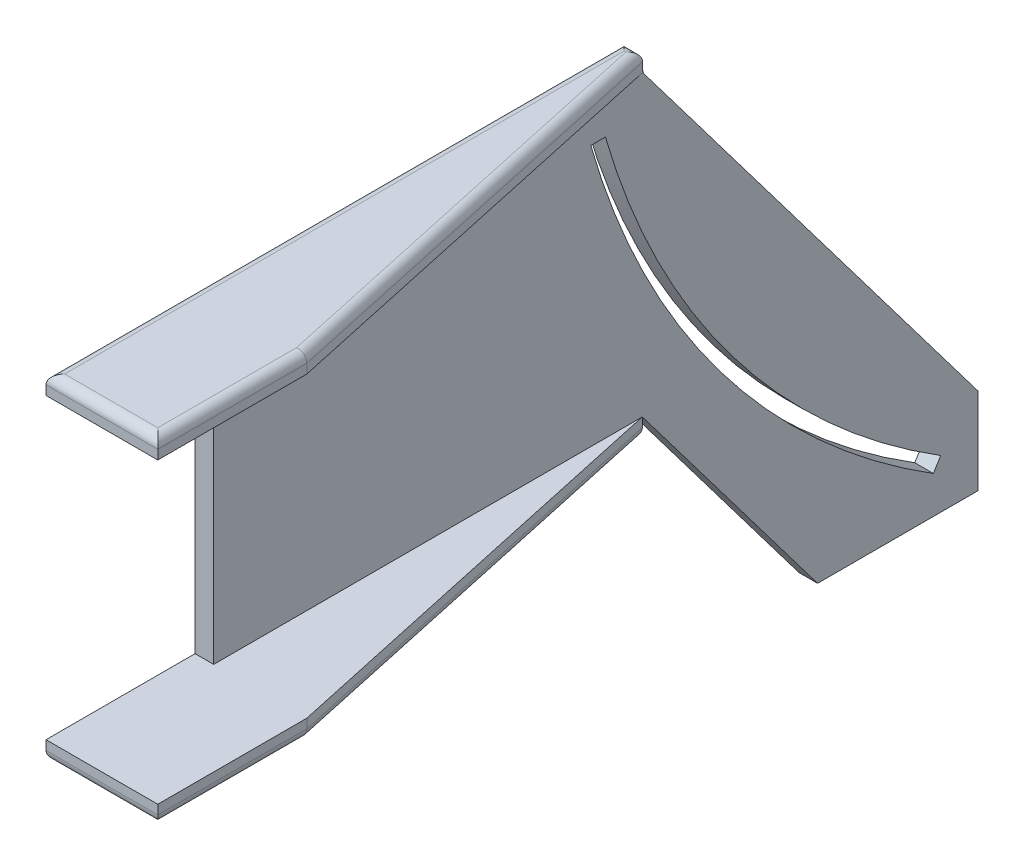
SolidWorks part; units mm, degrees
ref_plane "Front Plane" through (0, 0, 0) normal (0, 0, 1) x (1, 0, 0)
ref_plane "Top Plane" through (0, 0, 0) normal (0, 1, 0) x (1, 0, 0)
ref_plane "Right Plane" through (0, 0, 0) normal (1, 0, 0) x (0, 0, -1)
sketch "Sketch1" plane through (0, 0, 0) normal (1, 0, 0) x (0, 0, -1)
  line L0 (-129.391, -36.576) -> (-126.9146, -36.576)
  line L1 (-71.0224, -114.1738) -> (-69.7646, -112.1518)
  line L2 (-120.5646, -30.226) -> (-63.4146, -105.8018)
  line L3 (-193.675, -30.226) -> (-120.5646, -30.226)
  line L4 (-193.675, -30.226) -> (-193.675, -81.026)
  line L5 (-90.7526, -120.5238) -> (-63.4146, -120.5238)
  line L6 (-63.4146, -105.8018) -> (-63.4146, -120.5238)
  line L7 (-193.675, -81.026) -> (-120.6206, -81.026)
  line L8 (-120.6206, -81.026) -> (-90.7526, -120.5238)
  arc A0 (-126.9146, -36.576) -> (-69.7646, -112.1518) centre (0, 0) ccw
  arc A1 (-129.391, -36.576) -> (-71.0224, -114.1738) centre (0, 0) ccw
  point P14 (-128.1528, -36.576)
  dimension "D1" = 132.08
  dimension "D2" = 2.3813
  dimension "D3" = 193.675
  dimension "D4" = 6.35
  dimension "D5" = 6.35
  dimension "D6" = 6.35
  dimension "D7" = 6.35
  dimension "D8" = 6.35
  dimension "D9" = 57.15
  dimension "D10" = 30.226
  dimension "D11" = 0
  dimension "D12" = 50.8
extrude "Boss-Extrude1" add sketch "Sketch1" along normal blind 3.175
sketch "Sketch2" plane through (0, -30.226, 0) normal (0, 1, 0) x (1, 0, 0)
  line L0 (3.175, -193.675) -> (0, -193.675) construction
  line L1 (0, -120.5646) -> (3.175, -120.5646)
  line L2 (0, -120.5646) -> (0, -219.075)
  line L3 (0, -219.075) -> (19.05, -219.075)
  line L4 (19.05, -193.675) -> (19.05, -219.075)
  line L5 (3.175, -120.5646) -> (19.05, -193.675)
  point P8 (1.5875, -193.675)
  dimension "D1" = 25.4
  dimension "D2" = 19.05
  dimension "D3" = 0
extrude "Boss-Extrude2" add sketch "Sketch2" along normal blind 3.175
fillet "Fillet1" radius 1.5875 6 edges at (1.5875, -27.051, 120.5646) (0, -27.051, 169.8198) (9.525, -27.051, 219.075) (19.05, -27.051, 206.375) (11.1125, -27.051, 157.1198) (1.5875, -30.226, 120.5646)
sketch "Sketch4" plane through (0, -81.026, 0) normal (0, -1, 0) x (1, 0, 0)
  line L0 (0, 120.6206) -> (3.175, 120.6206)
  line L1 (3.175, 120.6206) -> (19.05, 193.675)
  line L2 (19.05, 193.675) -> (19.05, 219.075)
  line L3 (19.05, 219.075) -> (0, 219.075)
  line L4 (0, 219.075) -> (0, 120.6206)
extrude "Boss-Extrude3" add sketch "Sketch4" along normal blind 3.175
fillet "Fillet2" radius 1.5875 5 edges at (9.525, -84.201, 219.075) (19.05, -84.201, 206.375) (11.1125, -84.201, 157.1478) (1.5875, -84.201, 120.6206) (0, -84.201, 169.8478)
